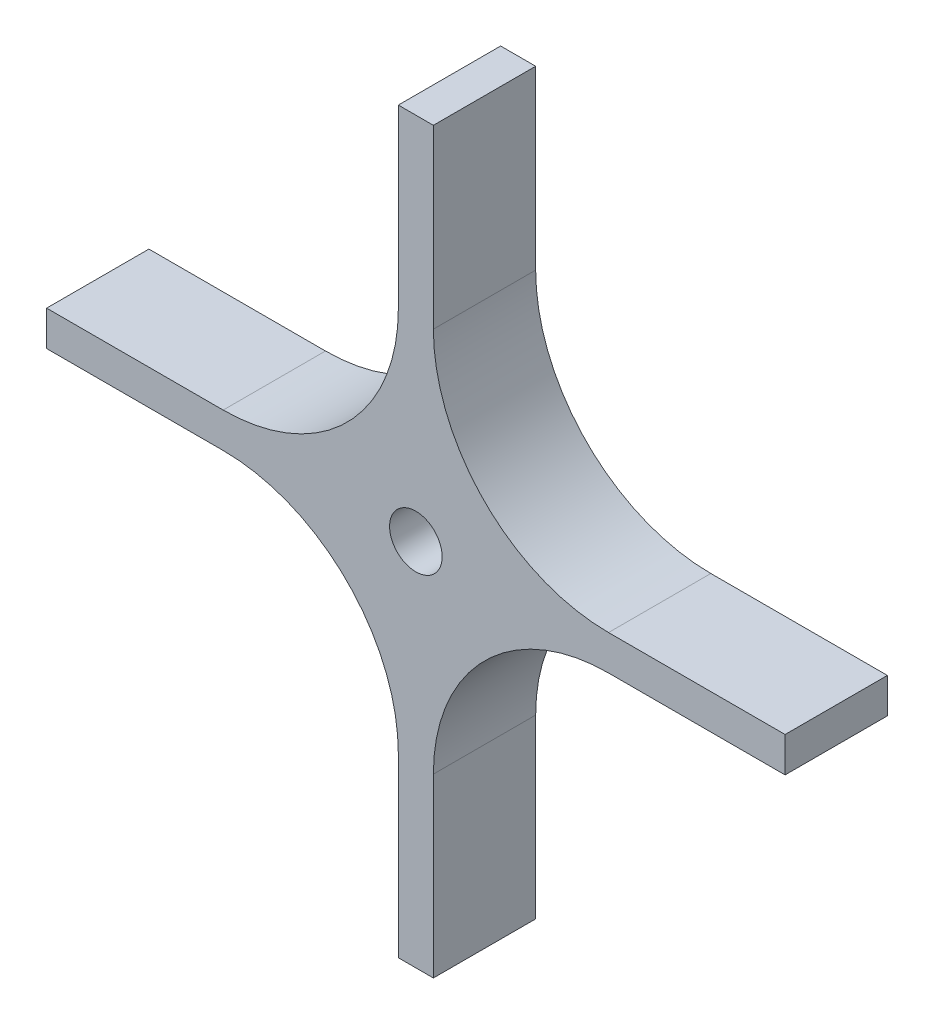
SolidWorks part; units mm, degrees
ref_plane "Front Plane" through (0, 0, 0) normal (0, 0, 1) x (1, 0, 0)
ref_plane "Top Plane" through (0, 0, 0) normal (0, 1, 0) x (1, 0, 0)
ref_plane "Right Plane" through (0, 0, 0) normal (1, 0, 0) x (0, 0, -1)
sketch "Sketch1" plane through (0, 0, 0) normal (0, 0, 1) x (1, 0, 0)
  line L0 (1.5875, -1.5875) -> (1.5875, -33.4645)
  line L1 (-1.5875, 33.4645) -> (1.5875, 33.4645)
  line L2 (-1.5875, 33.4645) -> (-1.5875, 1.5875)
  line L3 (-1.5875, -33.4645) -> (1.5875, -33.4645)
  line L4 (1.5875, 33.4645) -> (1.5875, 1.5875)
  line L5 (-1.5875, 33.4645) -> (1.5875, -33.4645) construction
  line L6 (-1.5875, -33.4645) -> (1.5875, 33.4645) construction
  line L7 (-33.4645, 1.5875) -> (-1.5875, 1.5875)
  line L8 (-33.4645, 1.5875) -> (-33.4645, -1.5875)
  line L9 (-33.4645, -1.5875) -> (-1.5875, -1.5875)
  line L10 (33.4645, 1.5875) -> (33.4645, -1.5875)
  line L11 (-33.4645, 1.5875) -> (33.4645, -1.5875) construction
  line L12 (-33.4645, -1.5875) -> (33.4645, 1.5875) construction
  line L13 (1.5875, -1.5875) -> (33.4645, -1.5875)
  line L14 (1.5875, 1.5875) -> (33.4645, 1.5875)
  line L15 (-1.5875, -1.5875) -> (-1.5875, -33.4645)
  circle A0 centre (17.526, 17.526) radius 15.9385 construction
  circle A1 centre (0, 0) radius 42.8625 construction
  point P0 (0, 0)
  point P6 (0, 0)
  dimension "D3" = 31.877
  dimension "D4" = 85.725
  dimension "D1" = 3.175
  dimension "D2" = 3.175
extrude "Boss-Extrude1" add sketch "Sketch1" along normal mid plane 9.271 contours L7 L2 L1 L4 L14 L10 L13 L0 L3 L15 L9 L8
fillet "Fillet1" radius 15.875 4 edges at (-1.5875, -1.5875, 0) (-1.5875, 1.5875, 0) (1.5875, -1.5875, 0) (1.5875, 1.5875, 0)
sketch "Sketch2" plane through (0, 0, 4.6355) normal (0, 0, 1) x (1, 0, 0)
  circle A0 centre (0, 0) radius 42.8625
hole_wizard "3/16 (0.1875) Diameter Hole1" positions "Sketch3" profile "Sketch4" hole size "3/16" standard "ANSI Inch" end condition through all
sketch "Sketch3" plane through (0, 0, 4.6355) normal (0, 0, 1) x (1, 0, 0)
  point P0 (0, 0)
sketch "Sketch4" plane through (0, 0, 4.6355) normal (1, 0, 0) x (0, -1, 0)
  line L0 (0, 0) -> (0, 9.271)
  line L1 (0, 9.271) -> (2.3812, 9.271)
  line L2 (2.3812, 9.271) -> (2.3812, 0)
  line L5 (2.3812, 0) -> (0, 0)
  line L11 (0, -6.35) -> (0, 107.95) construction
  dimension "Thru Hole Dia." = 4.7625
  dimension "Thru Hole Depth" = 9.271
